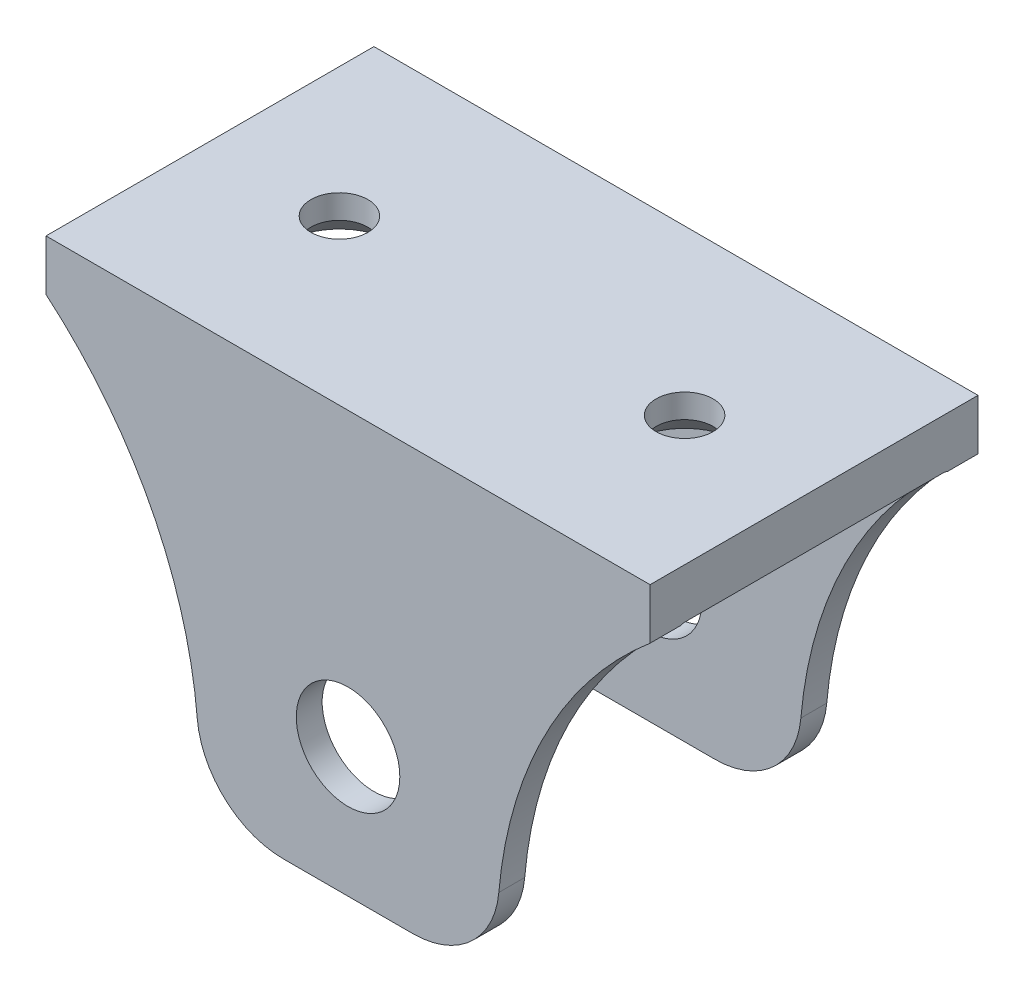
SolidWorks part; units mm, degrees
ref_plane "Płaszczyzna przednia" through (0, 0, 0) normal (0, 0, 1) x (1, 0, 0)
ref_plane "Płaszczyzna górna" through (0, 0, 0) normal (0, 1, 0) x (1, 0, 0)
ref_plane "Płaszczyzna prawa" through (0, 0, 0) normal (1, 0, 0) x (0, 0, -1)
sketch "Szkic1" plane through (0, 0, 0) normal (0, 0, 1) x (1, 0, 0)
  line L0 (0, 48.7686) -> (0, 42.8924)
  line L1 (27.4881, 0) -> (42.5119, 0)
  line L2 (0, 42.8924) -> (0, 48.7686)
  line L3 (0, 48.7686) -> (70, 48.7686)
  line L5 (35, 48.7686) -> (35, -11.9692) construction
  line L6 (70, 42.8924) -> (70, 48.7686)
  line L7 (70, 48.7686) -> (70, 42.8924)
  arc A0 (0, 42.8924) -> (17.5271, 9.1178) centre (-32.278, 4.7069) cw
  arc A1 (42.5119, 0) -> (52.4729, 9.1178) centre (42.5119, 10) ccw
  arc A2 (27.4881, 0) -> (17.5271, 9.1178) centre (27.4881, 10) cw
  arc A3 (70, 42.8924) -> (52.4729, 9.1178) centre (102.278, 4.7069) ccw
  circle A4 centre (35, 15) radius 6
  point P1 (35, 0)
  point P7 (52.5, 0)
  point P10 (35, 0)
  point P13 (35, 48.7686)
  point P15 (17.5, 0)
  point P18 (35, 48.7686)
  dimension "D1" = 50
  dimension "D3" = 10
  dimension "D2" = 15
extrude "Dodanie-wyciągnięcie1" add sketch "Szkic1" along normal blind 38 contours L3 L5 L1 | L5 L3 L0 A0 L1 region at (35, 29.1469, 0)
sketch "Szkic2" plane through (0, 0, 0) normal (0, -1, 0) x (1, 0, 0)
  line L14 (0, 3) -> (70, 3)
  line L16 (0, 35) -> (70, 35)
  line L23 (0, 35) -> (0, 3)
  line L24 (70, 35) -> (70, 3)
extrude "Wytnij-wyciągnięcie1" cut sketch "Szkic2" against normal blind 43
fillet "Zaokrąglenie1" radius 1 2 edges at (35, 43, 35) (35, 43, 3)
hole_wizard "Pogłębienie stożkowe pod M6 Śrubę z łbem soczewkowym1" positions "Szkic 3D1" profile "Szkic5" countersink size "M6" standard "ISO" end condition through all
sketch3d "Szkic 3D1"
  line L0 (0, 43, 34) -> (0, 43, 4) construction
  line L2 (70, 43, 19) -> (2.7425, 43, 19) construction
  point P0 (15, 43, 19)
  point P2 (55, 43, 19)
  dimension "D3" = 0
  dimension "D1" = 40
  dimension "D2" = 15
sketch "Szkic5" plane through (15, 43, 19) normal (1, 0, 0) x (0, 0, -1)
  line L0 (0, 0) -> (0, 5.7686)
  line L1 (0, 5.7686) -> (3.3, 5.7686)
  line L2 (3.3, 5.7686) -> (3.3, 3)
  line L3 (3.3, 3) -> (6.3, 0)
  line L5 (6.3, 0) -> (0, 0)
  line L6 (-3.3, 3) -> (-6.3, 0) construction
  line L11 (0, -6.35) -> (0, 107.95) construction
  dimension "Średnica otworu na wylot" = 6.6
  dimension "Głębokość otworu na wylot" = 5.7686
  dimension "Średnica zewnętrznego pogłębienia stożkowego" = 12.6
  dimension "Kąt zewnętrznego pogłębienia stożkowego" = 90
